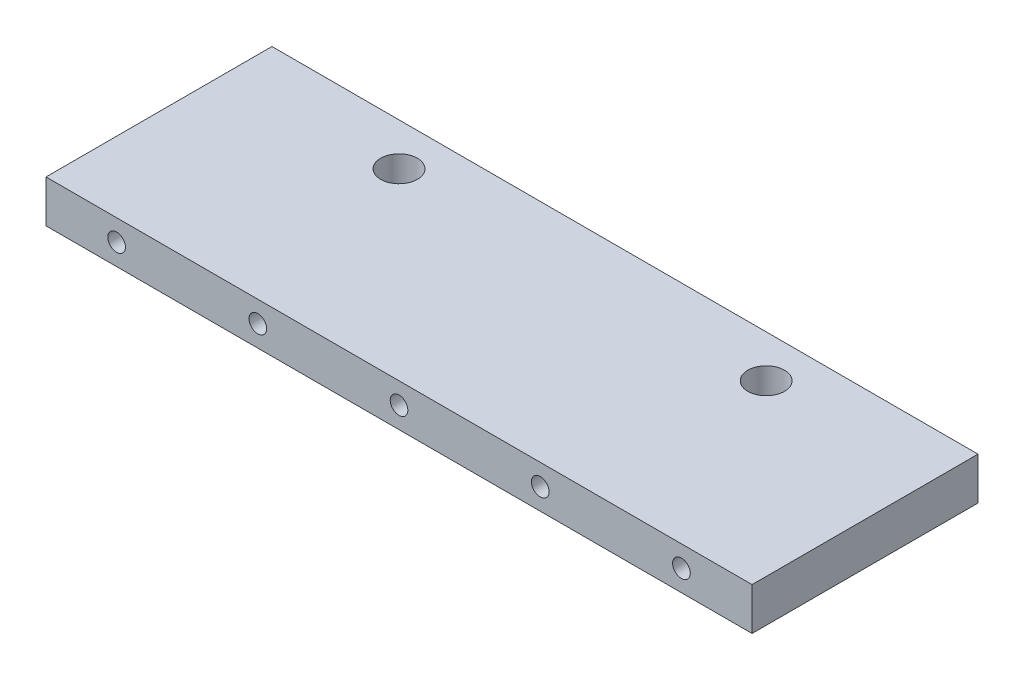
SolidWorks part; units mm, degrees
material "6061-T6 (SS)"
ref_plane "Front Plane" through (0, 0, 0) normal (0, 0, 1) x (1, 0, 0)
ref_plane "Top Plane" through (0, 0, 0) normal (0, 1, 0) x (1, 0, 0)
ref_plane "Right Plane" through (0, 0, 0) normal (1, 0, 0) x (0, 0, -1)
sketch "Sketch1" plane through (0, 0, 0) normal (0, 1, 0) x (1, 0, 0)
  line L1 (0, 0) -> (100, 0)
  line L2 (0, 0) -> (0, 32)
  line L3 (0, 32) -> (100, 32)
  line L4 (100, 0) -> (100, 32)
  dimension "D1" = 100
  dimension "D2" = 32
extrude "Boss-Extrude1" add sketch "Sketch1" along normal blind 6
sketch "Sketch5" plane through (0, 0, -32) normal (0, 0, -1) x (-1, 0, 0)
  line L1 (-100, 0) -> (0, 0) construction
  line L3 (-50, 3) -> (-50, 6) construction
  line L4 (-100, 6) -> (0, 6) construction
  point P0 (-90, 3)
  point P12 (-70, 3)
  point P13 (-50, 3)
  point P14 (-30, 3)
  point P15 (-10, 3)
  dimension "D1" = 3
  dimension "D2" = 5
  dimension "D3" = 20
hole_wizard "Tap Drill for M3 Tap1" positions "Sketch5" profile "Sketch7" hole size "M3" standard "DIN" end condition through all
sketch "Sketch7" plane through (90, 3, -32) normal (1, 0, 0) x (0, 1, 0)
  line L0 (0, 0) -> (0, 32)
  line L1 (0, 32) -> (1.25, 32)
  line L2 (1.25, 32) -> (1.25, 0)
  line L5 (1.25, 0) -> (0, 0)
  line L11 (0, -6.35) -> (0, 107.95) construction
  dimension "Thru Hole Dia." = 2.5
  dimension "Thru Hole Depth" = 32
sketch "Sketch10" plane through (0, 6, 0) normal (0, 1, 0) x (1, 0, 0)
  line L0 (0, 26) -> (100, 26) construction
  line L1 (0, 32) -> (0, 0) construction
  line L2 (100, 0) -> (100, 32) construction
  line L3 (76, 26) -> (24, 26)
  point P0 (24, 26)
  point P3 (76, 26)
  point P29 (50, 26)
  dimension "D1" = 52
  dimension "D2" = 6
hole_wizard "Tap Drill for M5 Helicoil1" positions "Sketch10" profile "Sketch11" hole size "M5x0.8" standard "DIN" end condition through all
sketch "Sketch11" plane through (24, 6, -26) normal (1, 0, 0) x (0, 0, 1)
  line L0 (0, 0) -> (0, 6)
  line L1 (0, 6) -> (2.6, 6)
  line L2 (2.6, 6) -> (2.6, 0)
  line L5 (2.6, 0) -> (0, 0)
  line L11 (0, -6.35) -> (0, 107.95) construction
  dimension "Thru Hole Dia." = 5.2
  dimension "Thru Hole Depth" = 6
